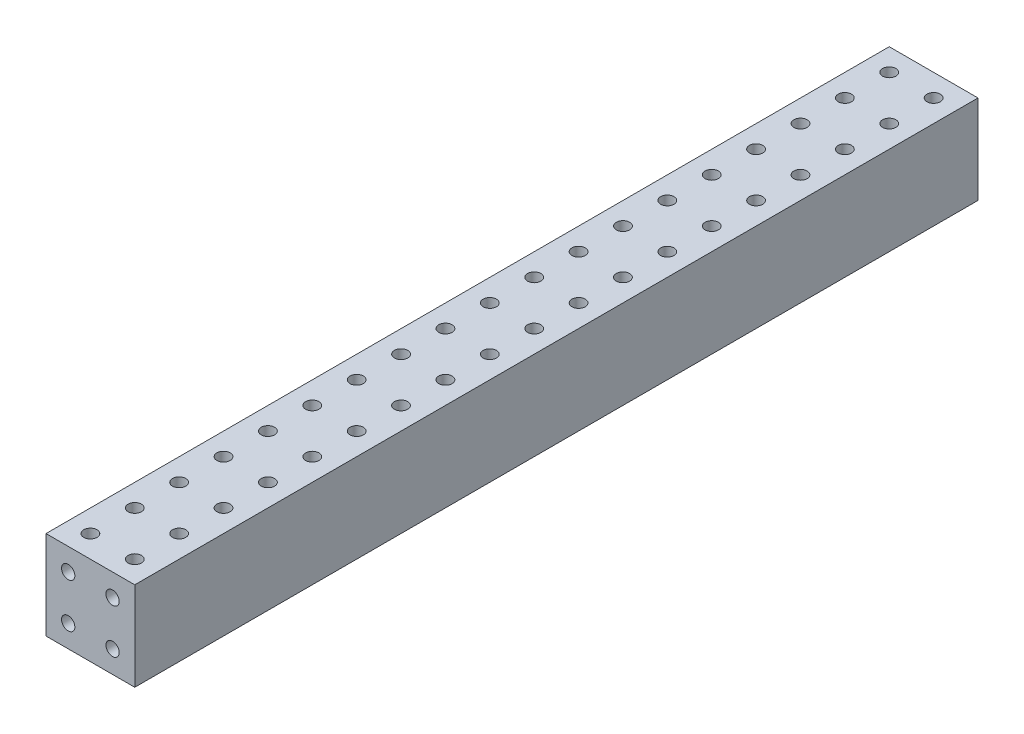
SolidWorks part; units mm, degrees
ref_plane "Front Plane" through (0, 0, 0) normal (0, 0, 1) x (1, 0, 0)
ref_plane "Top Plane" through (0, 0, 0) normal (0, 1, 0) x (1, 0, 0)
ref_plane "Right Plane" through (0, 0, 0) normal (1, 0, 0) x (0, 0, -1)
sketch "Sketch1" plane through (0, 0, 0) normal (0, 0, 1) x (1, 0, 0)
  line L1 (0, 0) -> (20, 0)
  line L2 (0, 0) -> (0, 20)
  line L3 (0, 20) -> (20, 20)
  line L4 (20, 0) -> (20, 20)
  dimension "D1" = 20
  dimension "D2" = 20
extrude "Boss-Extrude1" add sketch "Sketch1" along normal blind 190
sketch "Sketch2" plane through (0, 20, 0) normal (0, 1, 0) x (1, 0, 0)
  line L0 (20, -190) -> (20, 0) construction
  line L1 (20, -190) -> (0, -190) construction
  line L2 (20, -180) -> (9.1507, -180) construction
  line L3 (20, -170) -> (8.1861, -170) construction
  line L4 (20, -160) -> (8.5262, -160) construction
  line L5 (20, -150) -> (8.7307, -150) construction
  line L6 (20, -140) -> (9.1507, -140) construction
  line L7 (20, -130) -> (7.6382, -130) construction
  line L8 (20, -120) -> (8.5262, -120) construction
  line L9 (20, -110) -> (9.3805, -110) construction
  line L10 (20, -100) -> (9.8514, -100) construction
  line L11 (20, -90) -> (9.1507, -90) construction
  line L12 (20, -80) -> (12.2715, -80) construction
  line L13 (20, -70) -> (10.5723, -70) construction
  line L14 (20, -60) -> (7.6382, -60) construction
  line L15 (20, -50) -> (7.6382, -50) construction
  line L16 (20, -40) -> (9.8514, -40) construction
  line L17 (20, -30) -> (5.8594, -30) construction
  line L18 (20, -20) -> (9.1507, -20) construction
  line L19 (20, -10) -> (9.1507, -10) construction
  line L21 (10, -190) -> (10, -183.8181) construction
  circle A0 centre (15, -185) radius 1.5
  circle A1 centre (15, -175) radius 1.5
  circle A2 centre (15, -165) radius 1.5
  circle A3 centre (15, -155) radius 1.5
  circle A4 centre (15, -145) radius 1.5
  circle A5 centre (15, -135) radius 1.5
  circle A6 centre (15, -125) radius 1.5
  circle A7 centre (15, -115) radius 1.5
  circle A8 centre (15, -105) radius 1.5
  circle A9 centre (15, -95) radius 1.5
  circle A10 centre (15, -85) radius 1.5
  circle A11 centre (15, -75) radius 1.5
  circle A12 centre (15, -65) radius 1.5
  circle A13 centre (15, -55) radius 1.5
  circle A14 centre (15, -45) radius 1.5
  circle A15 centre (15, -35) radius 1.5
  circle A16 centre (15, -25) radius 1.5
  circle A17 centre (15, -15) radius 1.5
  circle A18 centre (15, -5) radius 1.5
  circle A19 centre (5, -5) radius 1.5
  circle A20 centre (5, -15) radius 1.5
  circle A21 centre (5, -25) radius 1.5
  circle A22 centre (5, -35) radius 1.5
  circle A23 centre (5, -45) radius 1.5
  circle A24 centre (5, -55) radius 1.5
  circle A25 centre (5, -65) radius 1.5
  circle A26 centre (5, -75) radius 1.5
  circle A27 centre (5, -85) radius 1.5
  circle A28 centre (5, -95) radius 1.5
  circle A29 centre (5, -105) radius 1.5
  circle A30 centre (5, -115) radius 1.5
  circle A31 centre (5, -125) radius 1.5
  circle A32 centre (5, -135) radius 1.5
  circle A33 centre (5, -145) radius 1.5
  circle A34 centre (5, -155) radius 1.5
  circle A35 centre (5, -165) radius 1.5
  circle A36 centre (5, -175) radius 1.5
  circle A37 centre (5, -185) radius 1.5
  dimension "D1" = 3
  dimension "D2" = 5
  dimension "D3" = 5
  dimension "D4" = 5
  dimension "D5" = 5
  dimension "D6" = 5
  dimension "D7" = 5
  dimension "D8" = 5
  dimension "D9" = 5
  dimension "D10" = 5
  dimension "D11" = 5
  dimension "D12" = 5
  dimension "D13" = 5
  dimension "D14" = 5
  dimension "D15" = 5
  dimension "D16" = 5
  dimension "D17" = 5
  dimension "D18" = 5
  dimension "D19" = 5
  dimension "D20" = 5
  dimension "D21" = 5
sketch "Sketch3" plane through (0, 0, 190) normal (0, 0, 1) x (1, 0, 0)
  line L0 (20, 20) -> (9.1507, 20) construction
  line L2 (20, 0) -> (20, 20) construction
  line L3 (20, 10) -> (11.9367, 10) construction
  line L4 (10, 0) -> (10, 7.5858) construction
  line L5 (0, 0) -> (20, 0) construction
  circle A0 centre (15, 15) radius 1.5
  circle A1 centre (15, 5) radius 1.5
  circle A2 centre (5, 5) radius 1.5
  circle A3 centre (5, 15) radius 1.5
  dimension "D3" = 3
  dimension "D1" = 5
  dimension "D2" = 5
extrude "Cut-Extrude2" cut sketch "Sketch2" against normal blind 20
extrude "Cut-Extrude3" cut sketch "Sketch3" against normal blind 10
